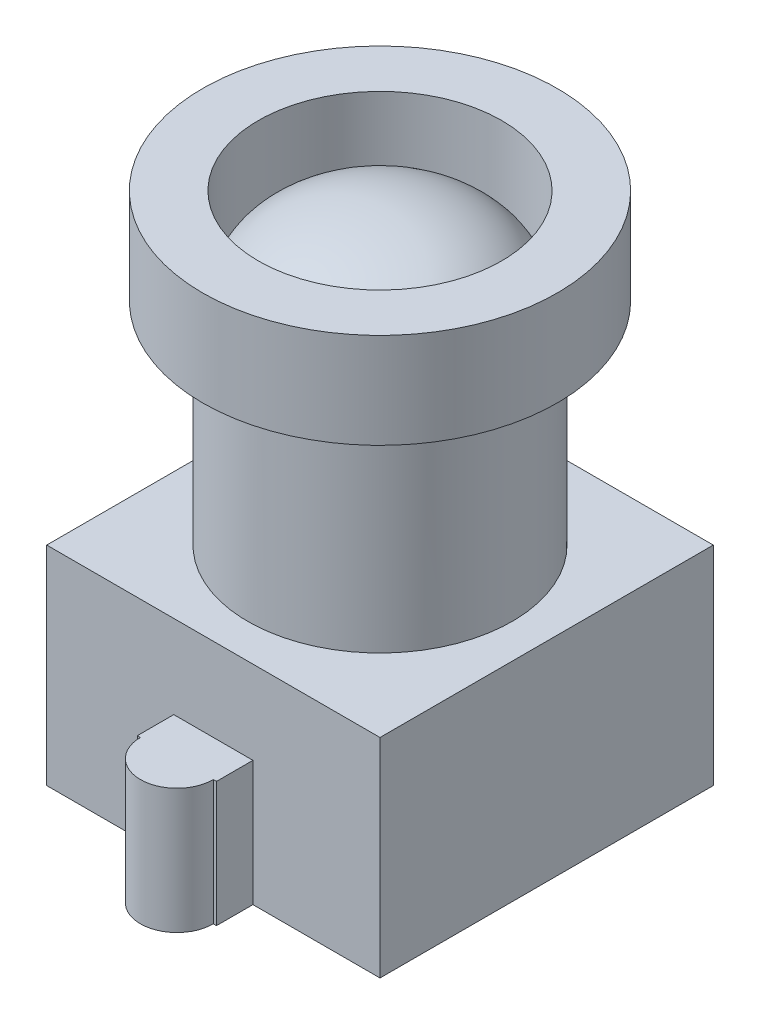
SolidWorks part; units mm, degrees
ref_plane "Front Plane" through (0, 0, 0) normal (0, 0, 1) x (1, 0, 0)
ref_plane "Top Plane" through (0, 0, 0) normal (0, 1, 0) x (1, 0, 0)
ref_plane "Right Plane" through (0, 0, 0) normal (1, 0, 0) x (0, 0, -1)
ref_plane "Plane1" through (0, 1.6, 0) normal (0, -1, 0) x (1, 0, 0)
sketch "Sketch1" plane through (0, 1.6, 0) normal (0, -1, 0) x (1, 0, 0)
  line L0 (8, -8) -> (8, 8)
  line L1 (8, 8) -> (-8, 8)
  line L2 (-8, 8) -> (-8, -8)
  line L3 (-8, -8) -> (8, -8)
extrude "ccd_base" add sketch "Sketch1" against normal blind 10
sketch "Sketch2" plane through (0, 1.6, 0) normal (0, -1, 0) x (1, 0, 0)
  line L0 (1.9, 9.75) -> (1.75, 9.75)
  line L1 (-1.75, 9.75) -> (-1.9, 9.75)
  line L2 (-1.9, 9.75) -> (-1.9, 8)
  line L3 (-1.9, 8) -> (1.9, 8)
  line L4 (1.9, 8) -> (1.9, 9.75)
  arc A0 (1.75, 9.75) -> (-1.75, 9.75) centre (0, 9.75) ccw
extrude "ccd_base_mount" add sketch "Sketch2" against normal blind 6
mirror "Mirror1" about plane through (0, 0, 0) normal (0, 0, 1) of "ccd_base_mount"
sketch "Sketch5" plane through (0, 11.6, 0) normal (0, 1, 0) x (1, 0, 0)
  circle A0 centre (0, 0) radius 6.35
  dimension "D1" = 12.7
extrude "lense_tube" add sketch "Sketch5" along normal blind 10.16
sketch "Sketch6" plane through (0, 21.76, 0) normal (0, 1, 0) x (1, 0, 0)
  circle A0 centre (0, 0) radius 8.509
  circle A1 centre (0, 0) radius 5.842
  dimension "D1" = 11.684
  dimension "D2" = 17.018
extrude "lense_rim" add sketch "Sketch6" along normal blind 4.572
dome "lense_glass" faces to dome 1 distance 3.81 reverse direction no elliptical dome yes face at (0, 21.76, 5.842) parameters "D1"=3.81
